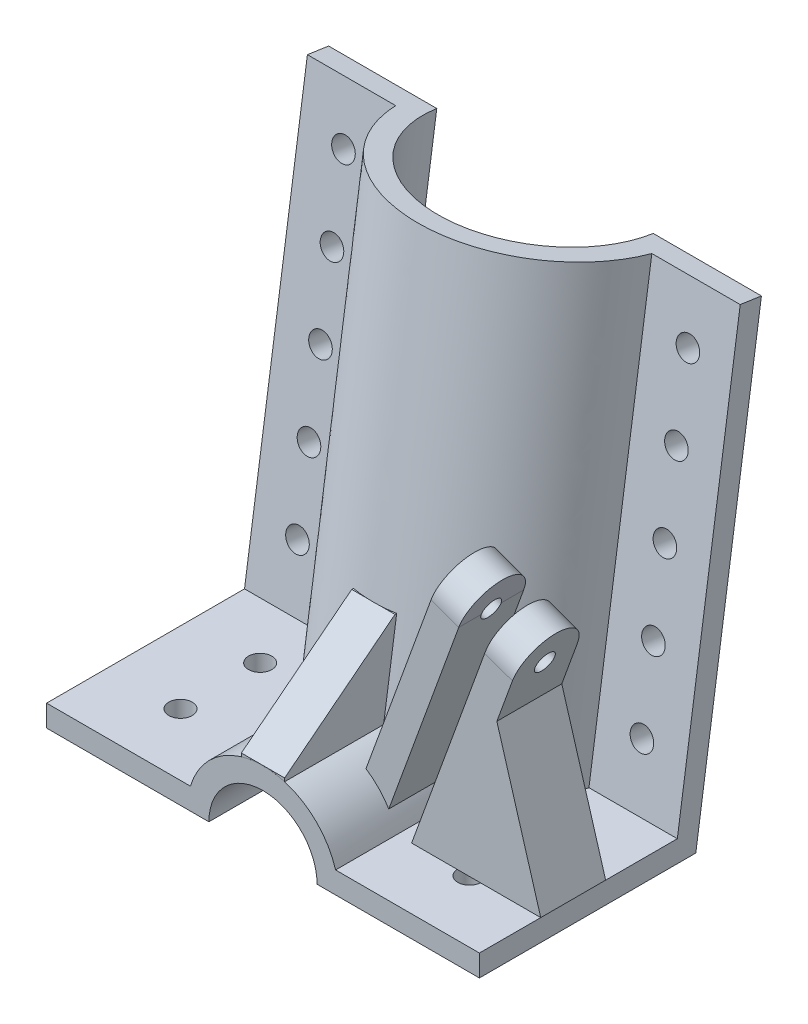
SolidWorks part; units mm, degrees
material "Nylon 6/10"
ref_plane "Front Plane" through (0, 0, 0) normal (0, 0, 1) x (1, 0, 0)
ref_plane "Top Plane" through (0, 0, 0) normal (0, 1, 0) x (1, 0, 0)
ref_plane "Right Plane" through (0, 0, 0) normal (1, 0, 0) x (0, 0, -1)
sketch "Sketch1" plane through (0, 0, 0) normal (0, 0, 1) x (1, 0, 0)
  line L0 (-12.5, 0) -> (-50, 0)
  line L1 (12.5, 0) -> (50, 0)
  line L2 (16.7705, 5) -> (50, 5)
  line L3 (-16.7705, 5) -> (-50, 5)
  line L4 (-50, 5) -> (-50, 0)
  line L5 (50, 5) -> (50, 0)
  arc A0 (-12.5, 0) -> (12.5, 0) centre (0, 0) cw
  arc A1 (-16.7705, 5) -> (16.7705, 5) centre (0, 0) cw
  dimension "D1" = 5
  dimension "D2" = 12.5
  dimension "D3" = 37.5
  dimension "D4" = 37.5
extrude "Boss-Extrude1" add sketch "Sketch1" along normal blind 50
sketch "Sketch2" plane through (0, 0, 0) normal (0, -1, 0) x (1, 0, 0)
  line L0 (-50, 0) -> (-12.5, 0) construction
  line L1 (12.5, 0) -> (50, 0) construction
  line L2 (-25, 0) -> (-50, 0)
  line L3 (25, 0) -> (50, 0)
  line L4 (29.5804, 5) -> (50, 5)
  line L5 (-29.5804, 5) -> (-50, 5)
  line L6 (-50, 5) -> (-50, 0)
  line L7 (50, 5) -> (50, 0)
  arc A0 (-25, 0) -> (25, 0) centre (0, 0) cw
  arc A1 (-29.5804, 5) -> (29.5804, 5) centre (0, 0) cw
  dimension "D1" = 5
ref_plane "Plane1" through (0, 0, 0) normal (-1, 0, 0) x (0, 0, 1)
sketch "Sketch3" plane through (0, 0, 0) normal (-1, 0, 0) x (0, 0, 1)
  line L0 (0, 0) -> (-15.8792, 108.8478)
sweep "Sweep1" add profiles "Sketch2" path "Sketch3"
sketch "Sketch4" plane through (0, 0, 0) normal (0, -0.1444, -0.9895) x (-1, 0, 0)
  line L5 (-50, 110) -> (-50, 105) construction
  line L10 (-50, 0) -> (-50, 110) construction
  line L12 (-50, 105) -> (75, 105)
  line L13 (-50, 105) -> (-50, 125.994)
  line L14 (-50, 125.994) -> (75, 125.994)
  line L15 (75, 105) -> (75, 125.994)
  dimension "D1" = 125
extrude "Cut-Extrude1" cut sketch "Sketch4" against normal blind 50
sketch "Sketch6" plane through (0, 0, 50) normal (0, 0, 1) x (1, 0, 0)
  line L0 (-12.5, 0) -> (12.5, 0)
  arc A0 (-12.5, 0) -> (12.5, 0) centre (0, 0) cw
  arc A1 (12.5, 0) -> (-12.5, 0) centre (0, 0) ccw construction
extrude "Cut-Extrude2" cut sketch "Sketch6" against normal blind 50
sketch "Sketch8" plane through (0, 0.7142, 4.8958) normal (0, 0.1444, 0.9895) x (1, 0, 0)
  line L0 (39.7902, 105) -> (39.7902, 0)
  line L1 (50, 105) -> (29.5804, 105) construction
  line L4 (0, 2.75) -> (0, -2.75) construction
  circle A10 centre (39.7902, 92) radius 2.7
  circle A11 centre (39.7902, 73.6) radius 2.7
  circle A12 centre (39.7902, 55.2) radius 2.7
  circle A13 centre (39.7902, 36.8) radius 2.7
  circle A14 centre (39.7902, 18.4) radius 2.7
  circle A20 centre (-39.7902, 18.4) radius 2.7
  circle A21 centre (-39.7902, 36.8) radius 2.7
  circle A22 centre (-39.7902, 55.2) radius 2.7
  circle A23 centre (-39.7902, 73.6) radius 2.7
  circle A24 centre (-39.7902, 92) radius 2.7
  dimension "D1" = 13
  dimension "D5" = 18.4
  dimension "D2" = 18.4
  dimension "D3" = 18.4
  dimension "D4" = 18.4
extrude "Cut-Extrude4" cut sketch "Sketch8" against normal up to next contours A10 | A11 | A12 | A13 | A14 | A24 | A23 | A22 | A21 | A20
ref_plane "Plane2" through (0, 17.5, 0) normal (0, -1, 0) x (-1, 0, 0)
sketch "Sketch11" plane through (0, 17.5, 0) normal (0, -1, 0) x (-1, 0, 0)
  line L0 (0, 0) -> (0, -57.4304) construction
  line L1 (-5, -23.657) -> (-5, -49.9978)
  line L2 (-5, -23.657) -> (5, -23.657)
  line L3 (0, -23.657) -> (0, -49.9978)
  line L4 (-5, -49.9978) -> (5, -49.9978)
  line L5 (5, -23.657) -> (5, -49.9978)
  dimension "D1" = 5
sketch "Sketch5" plane through (0, 103.9002, -15.1574) normal (0, 0.9895, -0.1444) x (1, 0, 0)
  line L18 (25, 0) -> (50, 0)
  line L19 (50, 0) -> (50, 3.1827)
  line L20 (50, 3.1827) -> (-62.8558, 3.1827)
  line L21 (-62.8558, 3.1827) -> (-62.8558, 0)
  line L22 (-62.8558, 0) -> (-25, 0)
  arc A1 (25, 0) -> (-25, 0) centre (0, 0) cw
sketch "Sketch13" plane through (0, 0, 0) normal (-1, 0, 0) x (0, 0, 1)
  line L0 (-15.1574, 103.9002) -> (0, 0)
  line L1 (0, 0) -> (1.5996, -10.9651)
sweep "Cut-Sweep1" cut profiles "Sketch5" path "Sketch13"
extrude "Boss-Extrude2" add sketch "Sketch11" along normal blind 2 and the other way blind 20 contours L1 L4 L5 L2
sketch "Sketch14" plane through (5, 0, 0) normal (1, 0, 0) x (0, 0, -1)
  line L0 (-24.4993, 37.5) -> (-49.9978, 17.5211)
  line L1 (-24.1097, 37.5) -> (-49.9978, 37.5) construction
  line L2 (-49.9978, 37.5) -> (-49.9978, 16.7705) construction
  line L3 (-49.9978, 17.5211) -> (-49.9978, 37.5)
  line L4 (-49.9978, 37.5) -> (-24.4993, 37.5)
extrude "Cut-Extrude6" cut sketch "Sketch14" against normal up to next
sketch "Sketch7" plane through (0, 5, 0) normal (0, 1, 0) x (1, 0, 0)
  line L0 (16.7705, -50) -> (50, -50)
  line L2 (33.3853, -50) -> (33.3853, -4.2706) construction
  line L5 (29.5804, -4.2706) -> (50, -4.2706) construction
  line L6 (0, 2.75) -> (0, -2.75) construction
  circle A6 centre (33.3853, -17.2706) radius 2.7
  circle A8 centre (33.3853, -35.6706) radius 2.7
  circle A9 centre (-33.3853, -35.6706) radius 2.7
  circle A10 centre (-33.3853, -17.2706) radius 2.7
  dimension "D1" = 13
  dimension "D2" = 18.4
  dimension "D3" = 14.3294
extrude "Cut-Extrude3" cut sketch "Sketch7" against normal up to next contours A10 | A9 | A6 | A8
ref_plane "Plane3" through (13.2018, -4.805, 0) normal (-0.9397, 0.342, 0) x (0, 0, -1)
ref_plane "Plane4" through (0, 4.7638, 32.6544) normal (0, -0.1444, -0.9895) x (-1, 0, 0)
sketch "Sketch15" plane through (13.2018, -4.805, 0) normal (-0.9397, 0.342, 0) x (0, 0, -1)
  line L13 (-35.8309, -44.2905) -> (-20.8309, -44.2905)
  line L14 (-35.8309, -44.2905) -> (-35.8309, -60.9915)
  line L16 (-20.8309, -44.2905) -> (-20.8309, -60.9915)
  arc A0 (-20.8309, -60.9915) -> (-35.8309, -60.9915) centre (-28.3309, -60.9915) cw
  circle A1 centre (-28.3309, -60.9915) radius 2.3
  dimension "D3" = 15
extrude "Boss-Extrude3" add sketch "Sketch15" along normal blind 10 and the other way blind 10 separate body
sketch "Sketch16" plane through (0, 0, 35.8309) normal (0, 0, 1) x (1, 0, 0)
  line L2 (43.459, 49.088) -> (24.6652, 55.9284) construction
  line L4 (31.0621, 53.6001) -> (25.35, 37.9063)
  line L5 (25.35, 37.9063) -> (28.3495, 36.8146)
  line L7 (27.5303, 34.5638) -> (28.3495, 36.8146) construction
  line L8 (28.3495, 36.8146) -> (34.0611, 52.5086)
  line L10 (28.3495, 36.8146) -> (34.0621, 52.5082)
  line L11 (31.349, 35.7228) -> (28.3495, 36.8146)
  line L12 (37.0611, 51.4167) -> (31.349, 35.7228)
  line L14 (31.0621, 53.6001) -> (33.7195, 60.8607)
  line L15 (33.7195, 60.8607) -> (39.532, 58.7332)
  line L16 (39.532, 58.7332) -> (37.0611, 51.4167)
extrude "Cut-Extrude7" cut sketch "Sketch16" against normal blind 15 contours L5 L4 L14 L15 L16 L12 L11
sketch "Sketch18" plane through (15.1482, 41.6194, 0) normal (-0.342, -0.9397, 0) x (0.9397, -0.342, 0)
  line L1 (4.049, 20.8309) -> (10.8565, 20.8309)
  line L2 (4.049, 20.8309) -> (4.049, 35.8309)
  line L3 (4.049, 35.8309) -> (10.8565, 35.8309)
  line L4 (10.8565, 20.8309) -> (10.8565, 35.8309)
extrude "Boss-Extrude5" add sketch "Sketch18" along normal blind 31
sketch "Sketch19" plane through (15.1482, 41.6194, 0) normal (-0.342, -0.9397, 0) x (0.9397, -0.342, 0)
  line L5 (17.2405, 20.8309) -> (24.049, 20.8309)
  line L6 (17.2405, 20.8309) -> (17.2405, 35.8309)
  line L7 (17.2405, 35.8309) -> (24.049, 35.8309)
  line L8 (24.049, 20.8309) -> (24.049, 35.8309)
extrude "Boss-Extrude6" add sketch "Sketch19" along normal blind 34
sketch "Sketch21" plane through (0, 5, 0) normal (0, 1, 0) x (1, 0, 0)
  line L5 (50, -50) -> (50, -4.2706) construction
  line L6 (28.165, -35.8309) -> (50, -35.8309)
  line L7 (28.165, -35.8309) -> (28.165, -20.8309)
  line L8 (28.165, -20.8309) -> (50, -20.8309)
  line L9 (50, -35.8309) -> (50, -20.8309)
sketch "Sketch22" plane through (22.5987, -8.2253, 0) normal (0.9397, -0.342, 0) x (0, 0, -1)
  line L0 (-20.8309, 60.9915) -> (-20.8309, 14.074) construction
  line L1 (-35.8309, 14.074) -> (-20.8309, 14.074)
  line L2 (-35.8309, 14.074) -> (-35.8309, 50.4775)
  line L3 (-35.8309, 50.4775) -> (-20.8309, 50.4775)
  line L4 (-20.8309, 14.074) -> (-20.8309, 50.4775)
loft "Loft4" add profiles "Sketch21", "Sketch22" connector at (28.165, 5, 35.8309) connector at (27.4123, 5, 35.8309)
